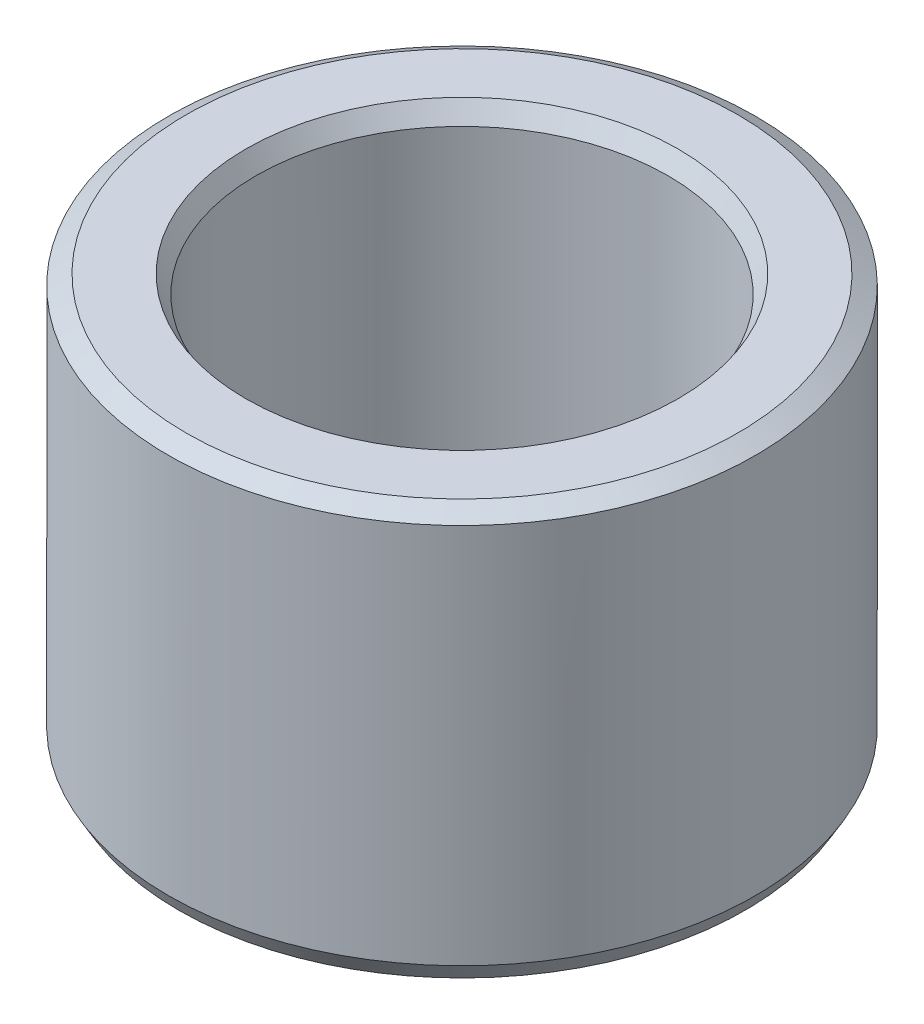
SolidWorks part; units mm, degrees
ref_plane "Front Plane" through (0, 0, 0) normal (0, 0, 1) x (1, 0, 0)
ref_plane "Top Plane" through (0, 0, 0) normal (0, 1, 0) x (1, 0, 0)
ref_plane "Right Plane" through (0, 0, 0) normal (1, 0, 0) x (0, 0, -1)
sketch "Sketch1" plane through (0, 0, 0) normal (0, 1, 0) x (1, 0, 0)
  circle A0 centre (0, 0) radius 55
  dimension "SLEEVE_OD" = 110
extrude "Boss-Extrude1" add sketch "Sketch1" along normal blind 76.6838
sketch "Sketch2" plane through (0, 0, 0) normal (0, 1, 0) x (1, 0, 0)
  circle A0 centre (0, 0) radius 38.5663
  dimension "BORE_D" = 77.1326
extrude "Cut-Extrude1" cut sketch "Sketch2" along normal through all
chamfer "Chamfer1" distance 1.9347 angle 60 4 edges at (0, 76.6838, 38.5663) (0, 0, 38.5663) (0, 0, 55) (0, 76.6838, 55) first distance on face at (0, 76.6838, 38.5663) first distance on face at (0, 0, 38.5663) first distance on face at (0, 76.6838, 55)
